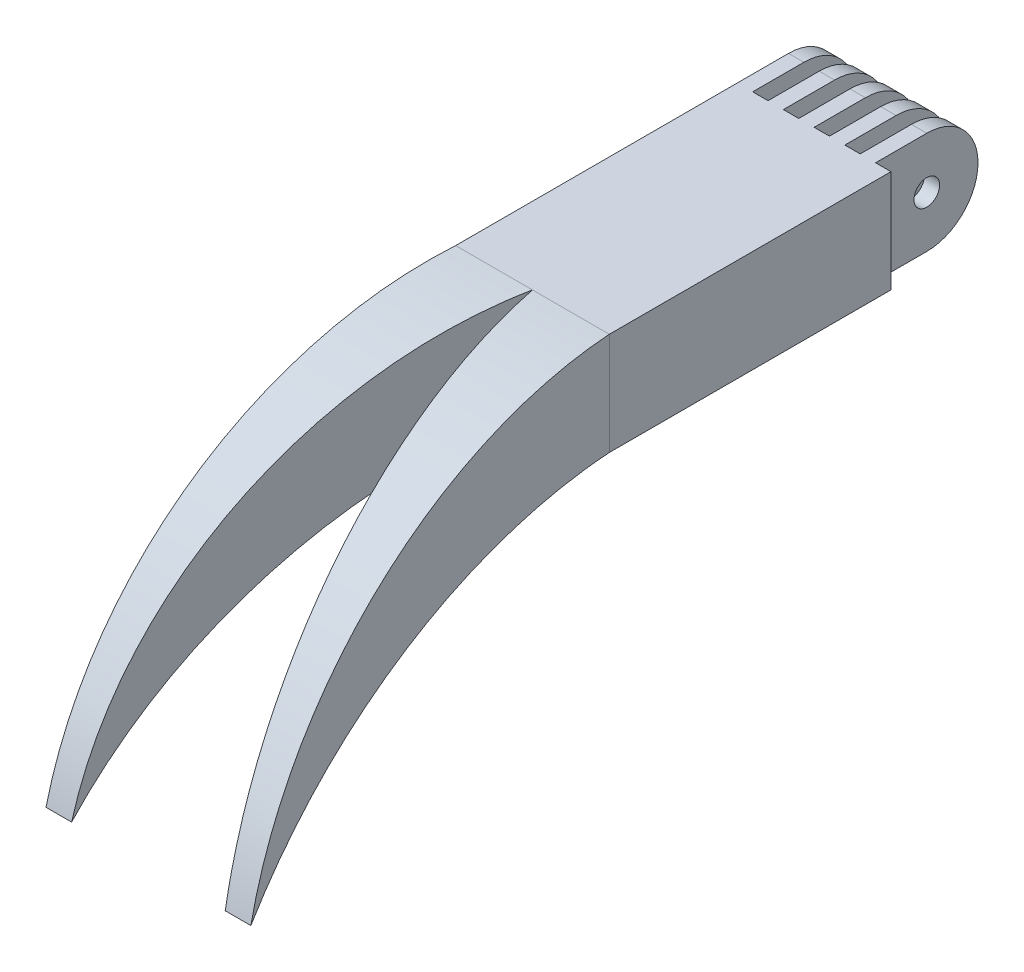
SolidWorks part; units mm, degrees
ref_plane "Plan de face" through (0, 0, 0) normal (0, 0, 1) x (1, 0, 0)
ref_plane "Plan de dessus" through (0, 0, 0) normal (0, 1, 0) x (1, 0, 0)
ref_plane "Plan de droite" through (0, 0, 0) normal (1, 0, 0) x (0, 0, -1)
sketch "Esquisse1" plane through (0, 0, 0) normal (1, 0, 0) x (0, 0, -1)
  line L1 (0, 10) -> (75, 10)
  line L2 (75, 10) -> (75, 30)
  line L3 (75, 30) -> (0, 30)
  arc A0 (0, 10) -> (-75, -30) centre (0, -80.3125) ccw
  arc A1 (0, 30) -> (-75, -30) centre (0, -46.875) ccw
  circle A2 centre (65, 20) radius 2.5
  dimension "D8" = 5
  dimension "D1" = 10
  dimension "D2" = 20
  dimension "D3" = 75
  dimension "D4" = 75
  dimension "D5" = 75
  dimension "D6" = 75
  dimension "D7" = 30
  dimension "D9" = 10
  dimension "D10" = 10
extrude "Boss.-Extru.1" add sketch "Esquisse1" along normal blind 40
sketch "Esquisse2" plane through (0, 30, 0) normal (0, 1, 0) x (1, 0, 0)
  line L0 (20, 0) -> (5, -75)
  line L1 (40, 0) -> (0, 0) construction
  line L2 (5, -75) -> (35, -75)
  line L3 (35, -75) -> (20, 0)
  line L4 (0, 75) -> (5, 75)
  line L5 (40, 75) -> (0, 75) construction
  line L6 (5, 75) -> (5, 0)
  line L7 (5, 0) -> (0, -75)
  line L8 (0, -75) -> (0, 75)
  line L9 (40, 75) -> (35, 75)
  line L10 (35, 75) -> (35, 0)
  line L11 (35, 0) -> (40, -75)
  line L12 (40, -75) -> (40, 75)
  dimension "D1" = 30
  dimension "D2" = 5
extrude "Enlèv. mat.-Extru.1" cut sketch "Esquisse2" against normal blind 60
fillet "Congé1" radius 10 2 edges at (20, 10, -75) (20, 30, -75)
sketch "Esquisse3" plane through (0, 30, 0) normal (0, 1, 0) x (1, 0, 0)
  line L0 (35, 82) -> (35, 55)
  line L1 (35, 65) -> (35, 0) construction
  line L2 (35, 55) -> (32, 55)
  line L3 (32, 55) -> (32, 80)
  line L4 (32, 80) -> (29, 80)
  line L5 (29, 80) -> (29, 55)
  line L6 (29, 55) -> (26, 55)
  line L7 (26, 55) -> (26, 80)
  line L8 (26, 80) -> (23, 80)
  line L9 (23, 80) -> (23, 55)
  line L10 (23, 55) -> (20, 55)
  line L11 (20, 55) -> (20, 80)
  line L12 (20, 80) -> (17, 80)
  line L13 (17, 80) -> (17, 55)
  line L14 (17, 55) -> (14, 55)
  line L15 (14, 55) -> (14, 80)
  line L16 (14, 80) -> (11, 80)
  line L17 (11, 80) -> (11, 55)
  line L18 (11, 55) -> (8, 55)
  line L19 (8, 55) -> (8, 82)
  line L20 (8, 82) -> (35, 82)
  line L21 (5, 75) -> (35, 75) construction
  dimension "D1" = 3
  dimension "D2" = 3
  dimension "D3" = 3
  dimension "D4" = 3
  dimension "D5" = 3
  dimension "D6" = 3
  dimension "D7" = 3
  dimension "D8" = 3
  dimension "D9" = 3
  dimension "D10" = 20
  dimension "D11" = 25
  dimension "D12" = 27
  dimension "D13" = 25
  dimension "D14" = 25
  dimension "D15" = 25
  dimension "D16" = 25
  dimension "D17" = 25
  dimension "D18" = 25
  dimension "D19" = 25
extrude "Enlèv. mat.-Extru.2" cut sketch "Esquisse3" against normal blind 20
